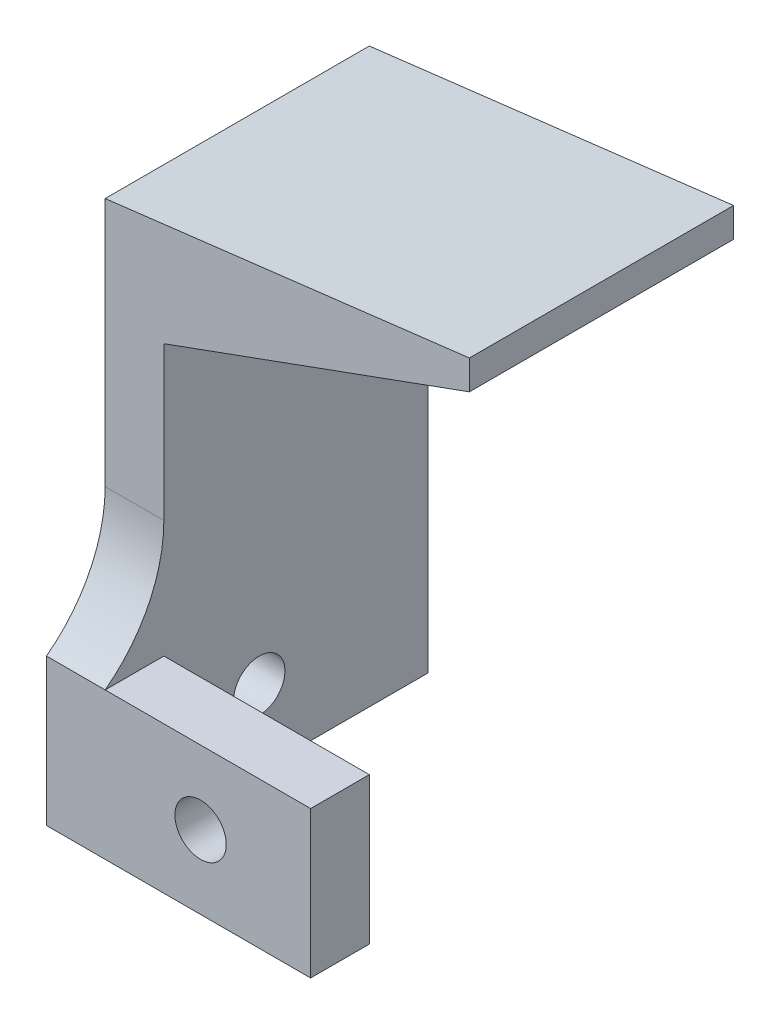
SolidWorks part; units mm, degrees
material "PLA"
ref_plane "前视基准面" through (0, 0, 0) normal (0, 0, 1) x (1, 0, 0)
ref_plane "上视基准面" through (0, 0, 0) normal (0, 1, 0) x (1, 0, 0)
ref_plane "右视基准面" through (0, 0, 0) normal (1, 0, 0) x (0, 0, -1)
sketch "草图1" plane through (0, 0, 0) normal (0, 0, 1) x (1, 0, 0)
  line L0 (0, 0) -> (4, 0)
  line L5 (4, 0) -> (4, 28.4324)
  line L6 (4, 28.4324) -> (24.8195, 30.9482) construction
  line L7 (24.8195, 30.9482) -> (24.8195, 37.9991) construction
  line L8 (24.8195, 37.9991) -> (0, 35)
  line L9 (0, 35) -> (0, 0)
  line L10 (4, 28.4324) -> (24.8195, 35.9991)
  line L11 (24.8195, 35.9991) -> (24.8195, 37.9991)
  dimension "D1" = 7
  dimension "D2" = 4
  dimension "D3" = 35
  dimension "D4" = 25
  dimension "D5" = 96.89
  dimension "D6" = 2
extrude "凸台-拉伸1" add sketch "草图1" along normal blind 18
sketch "草图2" plane through (0, 0, 0) normal (-1, 0, 0) x (0, 0, 1)
  line L0 (11.5, 0) -> (11.5, 35) construction
  line L3 (18, 35) -> (18, 0) construction
  line L4 (18, 35) -> (0, 35) construction
  line L5 (18, 0) -> (0, 0) construction
  circle A0 centre (11.5, 5) radius 1.75
  dimension "D2" = 3.5
  dimension "D1" = 5
  dimension "D3" = 6.5
extrude "切除-拉伸1" cut sketch "草图2" against normal blind 13
sketch "草图3" plane through (0, 0, 18) normal (0, 0, 1) x (1, 0, 0)
  line L1 (0, 0) -> (18, 0)
  line L2 (0, 0) -> (0, 10)
  line L3 (0, 10) -> (18, 10)
  line L4 (18, 0) -> (18, 10)
  dimension "D1" = 10
  dimension "D2" = 18
extrude "凸台-拉伸2" add sketch "草图3" along normal blind 4
sketch "草图10" plane through (0, 0, 18) normal (0, 0, -1) x (-1, 0, 0)
  circle A0 centre (-10.5, 5) radius 1.75
  dimension "D2" = 5
  dimension "D3" = 3.5
  dimension "D1" = 10.5
extrude "切除-拉伸2" cut sketch "草图10" against normal through all
fillet "圆角1" radius 10 1 edges at (2, 10, 18)
fillet "圆角2" [suppressed] radius 3
